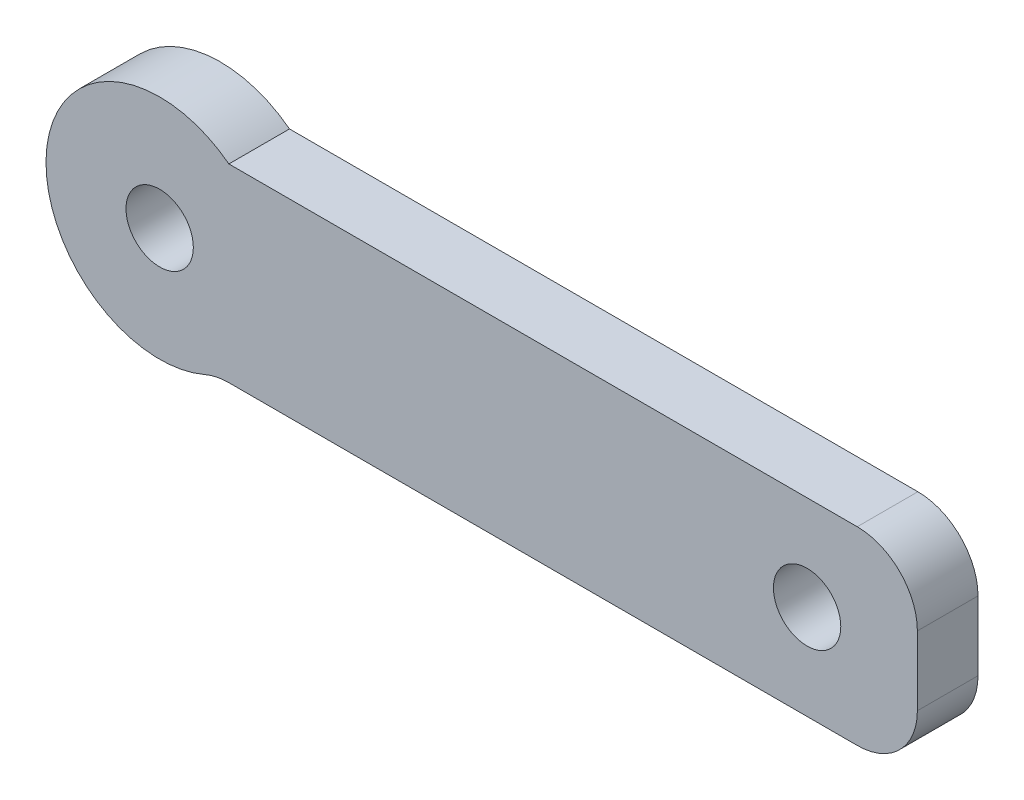
SolidWorks part; units mm, degrees
material "6061-T4 (SS)"
ref_plane "Front Plane" through (0, 0, 0) normal (0, 0, 1) x (1, 0, 0)
ref_plane "Top Plane" through (0, 0, 0) normal (0, 1, 0) x (1, 0, 0)
ref_plane "Right Plane" through (0, 0, 0) normal (1, 0, 0) x (0, 0, -1)
sketch "Sketch1" plane through (0, 0, 0) normal (0, 0, 1) x (1, 0, 0)
  line L1 (1.827, -2.6205) -> (18.4125, -2.6205)
  line L3 (1.827, 2.3795) -> (18.4125, 2.3795)
  line L4 (20, -1.033) -> (20, 0.792)
  arc A0 (1.827, 2.3795) -> (1.1948, -2.7518) centre (0, 0) ccw
  arc A1 (1.827, -2.6205) -> (1.1948, -2.7518) centre (1.827, -4.208) ccw
  arc A3 (18.4125, -2.6205) -> (20, -1.033) centre (18.4125, -1.033) ccw
  arc A4 (18.4125, 2.3795) -> (20, 0.792) centre (18.4125, 0.792) cw
  point P7 (0, 2.4637)
  point P12 (20, -2.6205)
  point P15 (20, 2.3795)
  point P16 (0.3574, -2.458)
  point P17 (0.8189, 2.8861)
  point P18 (1.0358, 2.1185)
  dimension "D2" = 6
  dimension "D4" = 1.5875
  dimension "D5" = 1.5875
  dimension "D1" = 20
  dimension "D3" = 5
extrude "Boss-Extrude1" add sketch "Sketch1" along normal blind 1.6002
hole_wizard "#0 Clearance Hole1" positions "Sketch2" profile "Sketch3" hole size "#0" standard "ANSI Inch" end condition through all
sketch "Sketch2" plane through (0, 0, 1.6002) normal (0, 0, 1) x (1, 0, 0)
  line L2 (0, 0) -> (8.4844, -8.6049) construction
  line L3 (8.4844, -8.6049) -> (17.0893, -0.1205) construction
  line L5 (17.0893, 2.3795) -> (17.0893, -2.6205) construction
  line L6 (1.827, -2.6205) -> (18.4125, -2.6205) construction
  line L8 (18.4125, 2.3795) -> (1.827, 2.3795) construction
  point P0 (0, 0)
  point P4 (17.0893, -0.1205)
  point P31 (14.1421, 2.525)
  point P34 (14.1375, -2.5)
  point P35 (0, 0)
  point P36 (9.0502, -9.1707)
  point P37 (0, 0)
sketch "Sketch3" plane through (0, 0, 1.6002) normal (1, 0, 0) x (0, -1, 0)
  line L0 (0, 0) -> (0, 1.6002)
  line L1 (0, 1.6002) -> (0.889, 1.6002)
  line L2 (0.889, 1.6002) -> (0.889, 0)
  line L5 (0.889, 0) -> (0, 0)
  line L11 (0, -6.35) -> (0, 107.95) construction
  dimension "Thru Hole Dia." = 1.778
  dimension "Thru Hole Depth" = 1.6002
